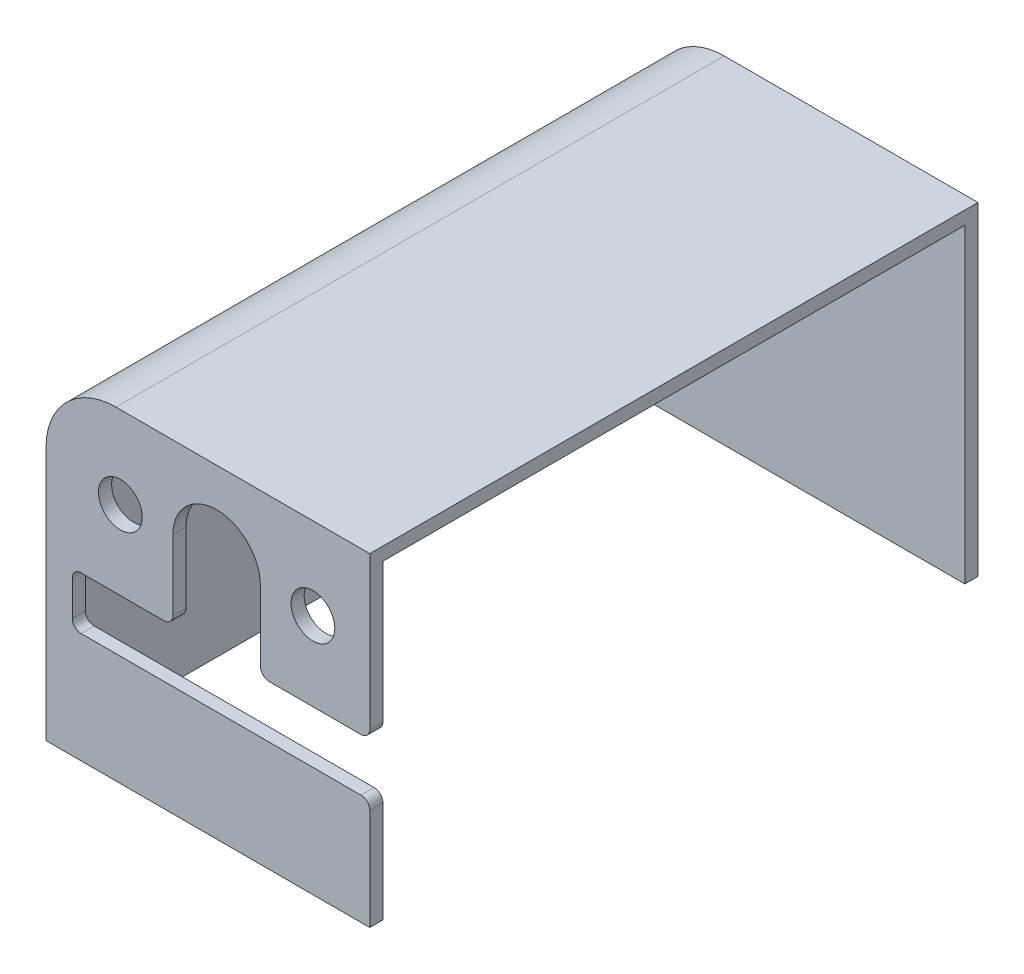
SolidWorks part; units mm, degrees
ref_plane "Front Plane" through (0, 0, 0) normal (0, 0, 1) x (1, 0, 0)
ref_plane "Top Plane" through (0, 0, 0) normal (0, 1, 0) x (1, 0, 0)
ref_plane "Right Plane" through (0, 0, 0) normal (1, 0, 0) x (0, 0, -1)
sketch "Sketch1" plane through (0, 0, 0) normal (0, 1, 0) x (1, 0, 0)
  line L0 (17.5, 35.5) -> (-18, 35.5)
  line L1 (-17.5, 35) -> (17.5, 35) construction
  line L2 (-17.5, 35) -> (-17.5, -35) construction
  line L3 (-17.5, -35) -> (17.5, -35) construction
  line L4 (17.5, 35) -> (17.5, -35) construction
  line L5 (-17.5, 35) -> (17.5, -35) construction
  line L6 (-17.5, -35) -> (17.5, 35) construction
  line L7 (-18, 35.5) -> (-18, -35.5)
  line L8 (-18, -35.5) -> (17.5, -35.5)
  line L9 (17.5, 37) -> (-19.5, 37)
  line L10 (-19.5, 37) -> (-19.5, -37)
  line L11 (-19.5, -37) -> (17.5, -37)
  line L12 (17.5, -35.5) -> (17.5, -37)
  line L13 (17.5, 37) -> (17.5, 35.5)
  point P0 (0, 0)
  dimension "D1" = 35
  dimension "D2" = 70
  dimension "D3" = 0.5
  dimension "D4" = 0.5
  dimension "D5" = 0.5
  dimension "D6" = 1.5
extrude "Boss-Extrude1" add sketch "Sketch1" along normal blind 22
sketch "Sketch2" plane through (0, 22, 0) normal (0, 1, 0) x (1, 0, 0)
  line L0 (-4, -27.5) -> (4, -27.5)
  line L1 (-19.5, -37) -> (28.4228, -37)
  line L2 (-19.5, -37) -> (-19.5, -32.5)
  line L3 (-19.5, -32.5) -> (28.4228, -32.5)
  line L4 (28.4228, -37) -> (28.4228, -32.5)
  line M5 (-19.5, 37) -> (-19.5, -37)
  line M6 (-19.5, -37) -> (17.5, -37)
  line M7 (17.5, -37) -> (17.5, -35.5)
  line M8 (17.5, -35.5) -> (-18, -35.5)
  line M9 (-18, -35.5) -> (-18, 35.5)
  dimension "D1" = 5
extrude "Cut-Extrude1" cut sketch "Sketch2" against normal through all both and the other way through all contours L1 L4 L3 M9 M8 M7 | L3 M5 M6 M7 M8 M9 region at (-2.3313, 22, 36.0812) region at (7.0798, 22, 34.2368)
sketch "Sketch3" plane through (0, 22, 0) normal (0, 1, 0) x (1, 0, 0)
  line L0 (17.5, 35.5) -> (17.5, 37) construction
  line L1 (-18, -32.5) -> (17.5, -32.5)
  line L2 (-18, -32.5) -> (-18, -31)
  line L3 (-18, -31) -> (17.5, -31)
  line L4 (17.5, -32.5) -> (17.5, -31)
  dimension "D1" = 1.5
extrude "Boss-Extrude2" add sketch "Sketch3" against normal up to vertex (22 mm away) up to point (-19.5, 0, 32.5)
sketch "Sketch4" plane through (0, 22, 0) normal (0, 1, 0) x (1, 0, 0)
  line L6 (-19.5, -32.5) -> (17.5, -32.5)
  line L11 (-18, -31) -> (-18, 35.5)
  line L12 (-18, 35.5) -> (17.5, 35.5)
  line L13 (17.5, 35.5) -> (17.5, 37)
  line L14 (17.5, 37) -> (-19.5, 37)
  line L15 (-19.5, 37) -> (-19.5, -32.5)
  line L19 (-18, -31) -> (-18, 35.5)
  line L20 (-18, 35.5) -> (17.5, 35.5)
  line L21 (17.5, 35.5) -> (17.5, 37)
  line L22 (17.5, 37) -> (-19.5, 37)
  line L23 (-19.5, 37) -> (-19.5, -32.5)
  line L31 (-19.5, -32.5) -> (17.5, -32.5)
  line L33 (17.5, -32.5) -> (17.5, -31)
  line L34 (17.5, -32.5) -> (17.5, -31)
  line L35 (17.5, -31) -> (-18, -31)
  line L36 (17.5, -31) -> (-18, -31)
  dimension "D1" = 0
extrude "Boss-Extrude3" add sketch "Sketch4" along normal blind 13.5
sketch "Sketch5" plane through (0, 35.5, 0) normal (0, 1, 0) x (1, 0, 0)
  line L1 (17.5, 37) -> (-19.5, 37)
  line L2 (17.5, 37) -> (17.5, -32.5)
  line L3 (17.5, -32.5) -> (-19.5, -32.5)
  line L4 (-19.5, 37) -> (-19.5, -32.5)
extrude "Boss-Extrude4" add sketch "Sketch5" along normal blind 1.5
fillet "Fillet1" radius 8 2 edges at (-18, 35.5, -2.25) (-19.5, 37, -2.25)
sketch "Sketch6" plane through (0, 0, 32.5) normal (0, 0, 1) x (1, 0, 0)
  line L0 (17.5, 0) -> (17.5, 37) construction
  line L5 (-16.5, 18.6) -> (17.5, 18.6)
  line L6 (-16.5, 18.6) -> (-16.5, 13.6)
  line L8 (17.5, 18.6) -> (17.5, 15.5285)
  line L10 (49.9164, 12.6) -> (17.5, 18.6) construction
  line L11 (-19.5, 0) -> (-19.5, 29) construction
  line L12 (-12.5, 12.6) -> (12.5, 12.6) construction
  line L13 (5, 18.6) -> (5, 27.6)
  line L14 (-5, 27.6) -> (-5, 18.6)
  line L15 (-11, 27.6) -> (11, 27.6) construction
  line L16 (-16.5, 13.6) -> (-16.5, 12.6)
  line L17 (-16.5, 12.6) -> (17.5, 12.6)
  line L18 (17.5, 12.6) -> (17.5, 15.5285)
  line L19 (-8.5, 14.6) -> (8.5, 14.6) construction
  line L20 (8.5, 14.6) -> (-8.5, 14.6) construction
  line L21 (-12.5, 16.6) -> (-8.5, 16.6) construction
  line L22 (-12.5, 16.6) -> (12.5, 16.6) construction
  arc A0 (5, 27.6) -> (-5, 27.6) centre (0, 27.6) ccw
  circle A1 centre (-11, 27.6) radius 2.5
  circle A2 centre (11, 27.6) radius 2.5
  point P0 (49.9164, 12.6)
  point P23 (0, 27.6)
  line M9 (17.5, 0) -> (17.5, 37)
  dimension "D3" = 5
  dimension "D5" = 5
  dimension "D1" = 3
  dimension "D2" = 5
  dimension "D4" = 9
  dimension "D6" = 22
  dimension "D7" = 2
  dimension "D8" = 2
extrude "Cut-Extrude2" cut sketch "Sketch6" against normal blind 1.5 contours L13 A0 L14 L5 | L6 L5 M9 | A2 | A1 region at (0.5, 15.6, 32.5) region at (0, 25.1117, 32.5) region at (-11, 27.6, 32.5) region at (11, 27.6, 32.5)
fillet "Fillet2" radius 1 6 edges at (17.5, 18.6, 31.75) (-16.5, 18.6, 31.75) (5, 18.6, 31.75) (-5, 18.6, 31.75) (17.5, 12.6, 31.75) (-16.5, 12.6, 31.75)
sketch "Sketch7" plane through (-19.5, 0, 0) normal (-1, 0, 0) x (0, 0, 1)
  circle A0 centre (25, 1.5) radius 0.75
  circle A1 centre (0, 1.5) radius 0.75
  circle A2 centre (-25, 1.5) radius 0.75
extrude "Cut-Extrude3" cut sketch "Sketch7" against normal through all both and the other way through all
